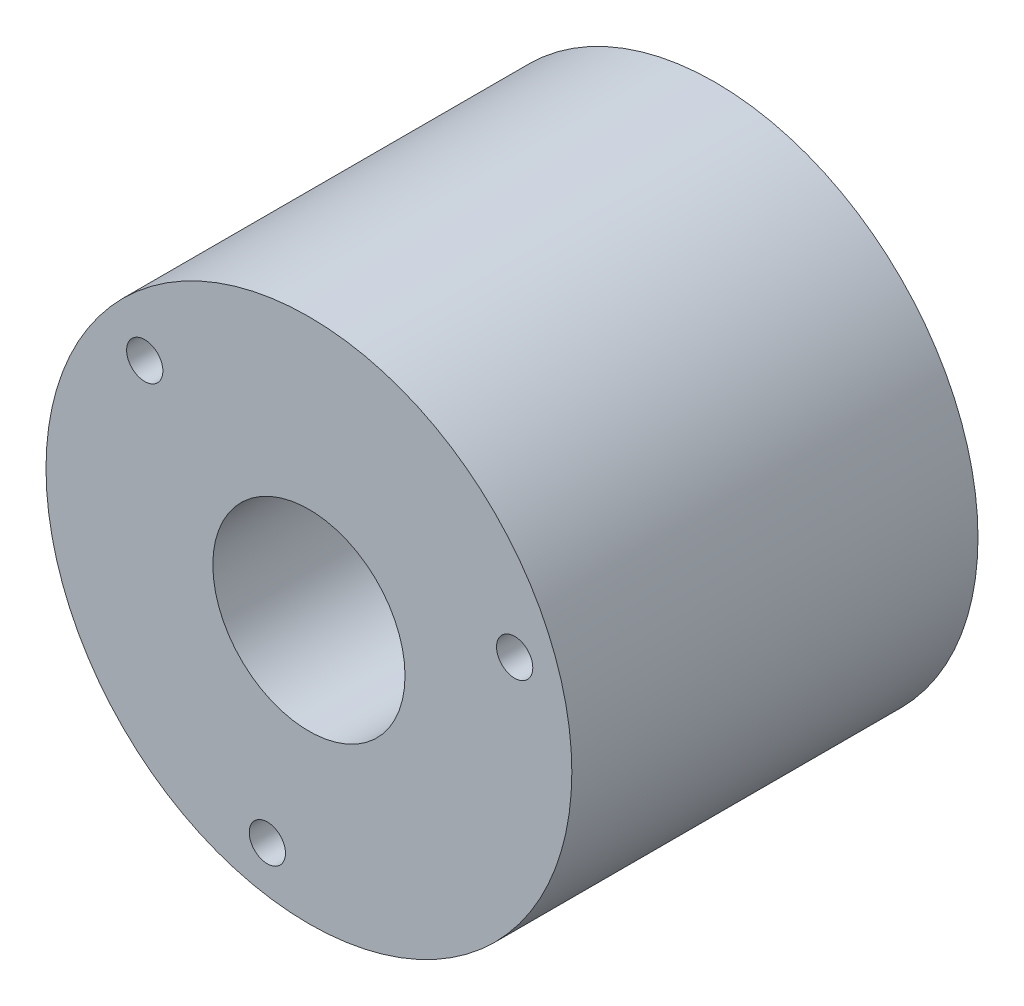
SolidWorks part; units mm, degrees
ref_plane "Ön Düzlem" through (0, 0, 0) normal (0, 0, 1) x (1, 0, 0)
ref_plane "Üst Düzlem" through (0, 0, 0) normal (0, 1, 0) x (1, 0, 0)
ref_plane "Sağ Düzlem" through (0, 0, 0) normal (1, 0, 0) x (0, 0, -1)
sketch "Sketch1" plane through (0, 0, 0) normal (0, 0, 1) x (1, 0, 0)
  circle A0 centre (0, 0) radius 36.25
  circle A1 centre (0, 0) radius 13.25
  dimension "D1" = 72.5
  dimension "D2" = 26.5
extrude "Boss-Extrude1" add sketch "Sketch1" along normal blind 48
sketch "Sketch2" plane through (0, 0, 0) normal (0, 0, -1) x (-1, 0, 0)
  circle A0 centre (0, 0) radius 36.25 construction
  circle A1 centre (0, 0) radius 36.25
  circle A2 centre (0, 0) radius 5.5
  dimension "D1" = 11
extrude "Boss-Extrude3" add sketch "Sketch2" along normal blind 8 and the other way blind 2.1786
sketch "Sketch3" plane through (0, 0, 48) normal (0, 0, 1) x (1, 0, 0)
  circle A0 centre (-5.7315, -29.4474) radius 2.5 construction
  circle A1 centre (-22.6364, 19.6873) radius 2.5 construction
  circle A2 centre (28.368, 9.7601) radius 2.5 construction
  circle A3 centre (-5.7315, -29.4474) radius 2.5
  circle A4 centre (-22.6364, 19.6873) radius 2.5
  circle A5 centre (28.368, 9.7601) radius 2.5
extrude "Cut-Extrude1" cut sketch "Sketch3" against normal through all
